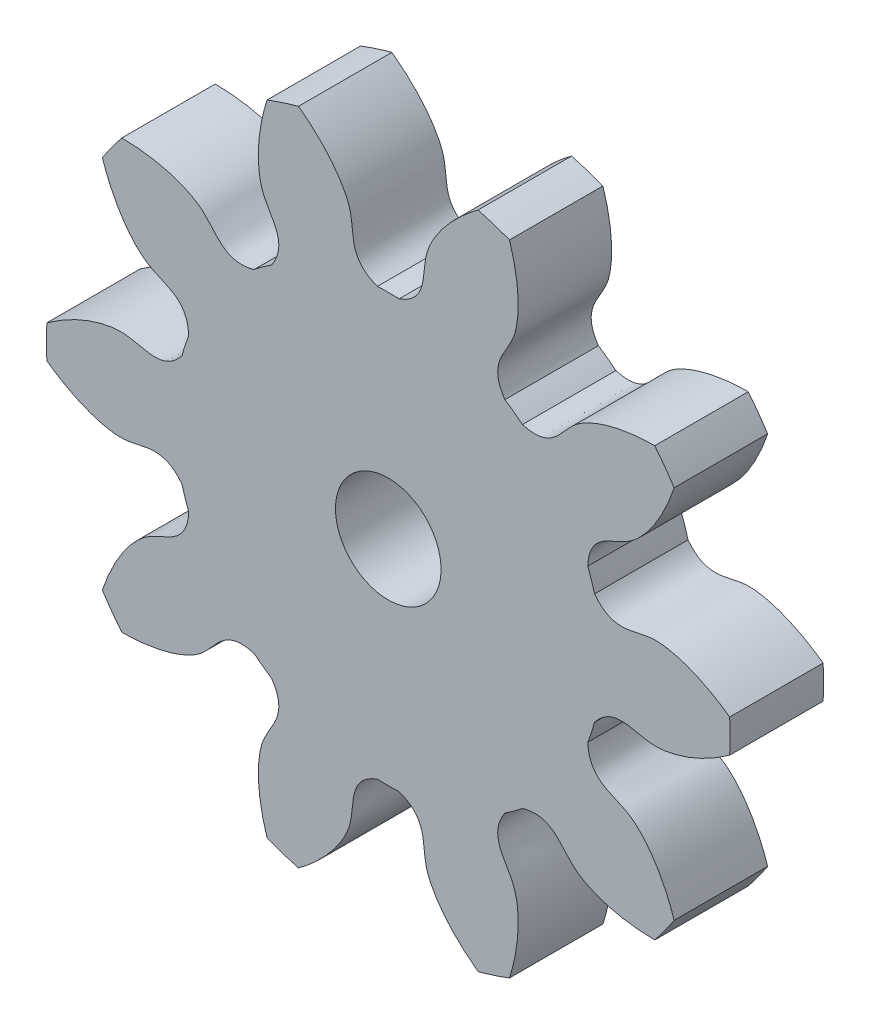
SolidWorks part; units mm, degrees
material "尼龙 6/10"
ref_plane "前视基准面" through (0, 0, 0) normal (0, 0, 1) x (1, 0, 0)
ref_plane "上视基准面" through (0, 0, 0) normal (0, 1, 0) x (1, 0, 0)
ref_plane "右视基准面" through (0, 0, 0) normal (1, 0, 0) x (0, 0, -1)
sketch "草图1" plane through (0, 0, 0) normal (0, 0, 1) x (1, 0, 0)
  circle A0 centre (0, 0) radius 4.2
extrude "凸台-拉伸1" add sketch "草图1" along normal blind 1.1486
ref_axis "基准轴1" through (0, 0, -1.5) along (0, 0, 1)
sketch "草图2" plane through (0, 0, 0) normal (0, 0, 1) x (1, 0, 0)
  line L0 (0, 0) -> (0, 4.2) construction
  circle A0 centre (0, 0) radius 4.2 construction
  arc A1 (0.1333, 2.6216) -> (-0.1333, 2.6216) centre (0, 0) ccw
  arc A2 (2.9775, 4.686) -> (-2.9775, 4.686) centre (0, 0) ccw
  spline S0 degree 3 poles (0.1333, 2.6216) (0.5078, 2.7584) (0.4017, 3.0594) (0.4821, 3.3073) (0.4862, 3.3191) (0.4909, 3.332) (0.4964, 3.3461) (0.5028, 3.3613) (0.5099, 3.3776) (0.5179, 3.3949) (0.5268, 3.4132) (0.5367, 3.4326) (0.5476, 3.4528) (0.5596, 3.474) (0.5726, 3.4961) (0.5868, 3.5191) (0.6021, 3.5429) (0.6186, 3.5674) (0.6364, 3.5927) (0.6555, 3.6187) (0.6759, 3.6453) (0.6976, 3.6726) (0.7207, 3.7004) (0.7453, 3.7288) (0.7712, 3.7576) (0.7987, 3.7869) (0.8276, 3.8166) (0.8581, 3.8466) (0.8901, 3.8769) (0.9237, 3.9074) (0.9588, 3.9381) (0.9956, 3.969) (1.0341, 3.9999) (1.0741, 4.0309) (1.1159, 4.0618) (1.1593, 4.0927) (1.2045, 4.1234) (1.2513, 4.154) (1.2998, 4.1843) (1.3501, 4.2143) (1.4021, 4.2439) (1.4559, 4.2731) (1.5114, 4.3019) (1.5686, 4.3301) (1.6276, 4.3577) (1.6883, 4.3846) (1.7508, 4.4109) (1.815, 4.4364) (1.8809, 4.461) (1.9486, 4.4848) (2.0179, 4.5076) (2.089, 4.5294) (2.1617, 4.5502) (2.2361, 4.5698) (2.3122, 4.5883) (2.3899, 4.6055) (2.4693, 4.6214) (2.5502, 4.6359) (2.6327, 4.6491) (2.7167, 4.6607) (2.8317, 4.6743) (2.9189, 4.682) (2.9775, 4.686) knots 0 0 0 0 0.201721 0.204697 0.208023 0.211699 0.215726 0.220102 0.224829 0.229906 0.235332 0.241109 0.247237 0.253714 0.260541 0.267719 0.275246 0.283124 0.291352 0.29993 0.308858 0.318136 0.327765 0.337743 0.348072 0.358751 0.36978 0.381158 0.392888 0.404967 0.417396 0.430176 0.443305 0.456785 0.470615 0.484795 0.499325 0.514205 0.529435 0.545016 0.560946 0.577227 0.593858 0.610839 0.62817 0.645851 0.663882 0.682264 0.700995 0.720077 0.739509 0.759291 0.779423 0.799905 0.820737 0.84192 0.863452 0.885335 0.907568 0.930151 0.953084 1 1 1 1
  spline S1 degree 3 poles (-0.1333, 2.6216) (-0.5078, 2.7584) (-0.4017, 3.0594) (-0.4821, 3.3073) (-0.4862, 3.3191) (-0.4909, 3.332) (-0.4964, 3.3461) (-0.5028, 3.3613) (-0.5099, 3.3776) (-0.5179, 3.3949) (-0.5268, 3.4132) (-0.5367, 3.4326) (-0.5476, 3.4528) (-0.5596, 3.474) (-0.5726, 3.4961) (-0.5868, 3.5191) (-0.6021, 3.5429) (-0.6186, 3.5674) (-0.6364, 3.5927) (-0.6555, 3.6187) (-0.6759, 3.6453) (-0.6976, 3.6726) (-0.7207, 3.7004) (-0.7453, 3.7288) (-0.7712, 3.7576) (-0.7987, 3.7869) (-0.8276, 3.8166) (-0.8581, 3.8466) (-0.8901, 3.8769) (-0.9237, 3.9074) (-0.9588, 3.9381) (-0.9956, 3.969) (-1.0341, 3.9999) (-1.0741, 4.0309) (-1.1159, 4.0618) (-1.1593, 4.0927) (-1.2045, 4.1234) (-1.2513, 4.154) (-1.2998, 4.1843) (-1.3501, 4.2143) (-1.4021, 4.2439) (-1.4559, 4.2731) (-1.5114, 4.3019) (-1.5686, 4.3301) (-1.6276, 4.3577) (-1.6883, 4.3846) (-1.7508, 4.4109) (-1.815, 4.4364) (-1.8809, 4.461) (-1.9486, 4.4848) (-2.0179, 4.5076) (-2.089, 4.5294) (-2.1617, 4.5502) (-2.2361, 4.5698) (-2.3122, 4.5883) (-2.3899, 4.6055) (-2.4693, 4.6214) (-2.5502, 4.6359) (-2.6327, 4.6491) (-2.7167, 4.6607) (-2.8317, 4.6743) (-2.9189, 4.682) (-2.9775, 4.686) knots 0 0 0 0 0.201721 0.204697 0.208023 0.211699 0.215726 0.220102 0.224829 0.229906 0.235332 0.241109 0.247237 0.253714 0.260541 0.267719 0.275246 0.283124 0.291352 0.29993 0.308858 0.318136 0.327765 0.337743 0.348072 0.358751 0.36978 0.381158 0.392888 0.404967 0.417396 0.430176 0.443305 0.456785 0.470615 0.484795 0.499325 0.514205 0.529435 0.545016 0.560946 0.577227 0.593858 0.610839 0.62817 0.645851 0.663882 0.682264 0.700995 0.720077 0.739509 0.759291 0.779423 0.799905 0.820737 0.84192 0.863452 0.885335 0.907568 0.930151 0.953084 1 1 1 1
extrude "切除-拉伸1" cut sketch "草图2" along normal through all
pattern_circular "阵列(圆周)1" count 10 every 36 about axis through (0, 0, -1.5) along (0, 0, 1) of "切除-拉伸1"
sketch "草图3" plane through (0, 0, 0) normal (0, 0, 1) x (1, 0, 0)
  circle A0 centre (0, 0) radius 3.5 construction
  dimension "Dn" = 7
scale "缩放比例1" scale about centroid uniform scaling yes scale factor 0.870588
sketch "草图7" plane through (0, 0, 1.0517) normal (0, 0, 1) x (1, 0, 0)
  circle A0 centre (0, 0) radius 0.5625
  dimension "D1" = 1.125
sketch "草图9" plane through (0, 0, 0.0743) normal (0, 0, -1) x (-1, 0, 0)
  circle A0 centre (0, 0) radius 0.565
  dimension "D1" = 1.13
extrude "切除-拉伸2" cut sketch "草图9" against normal through all
